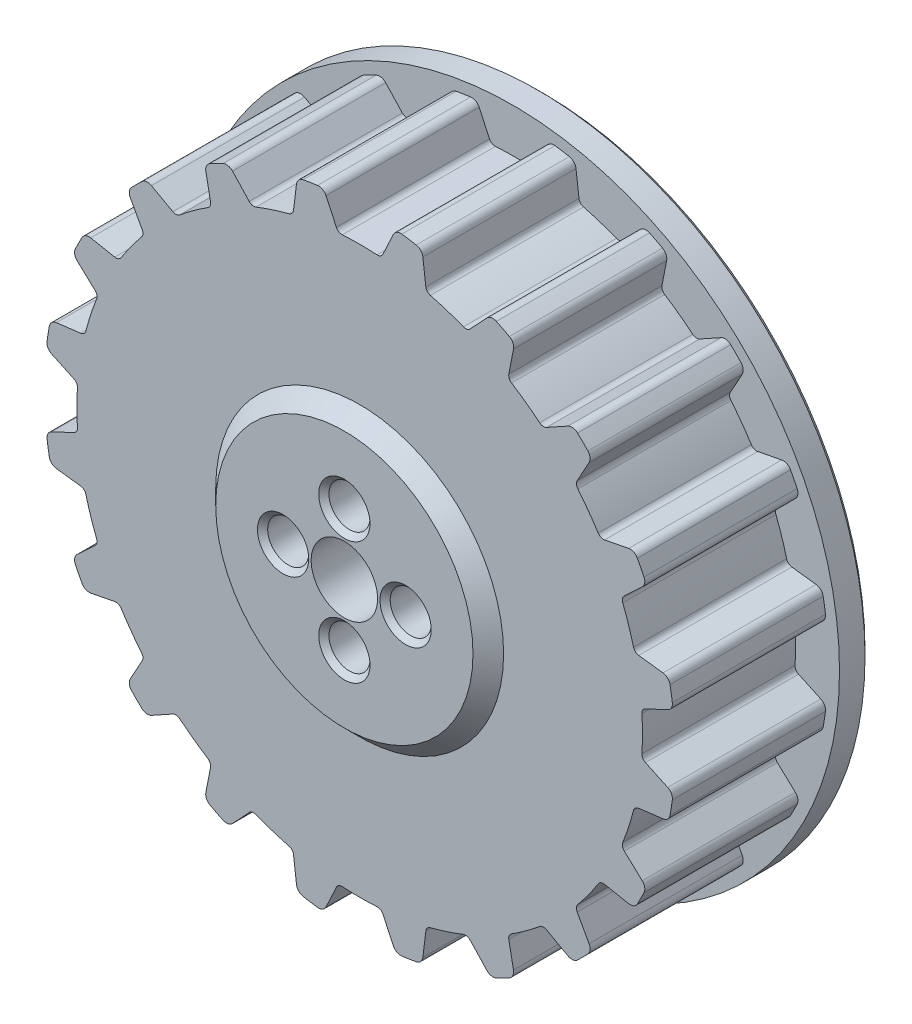
SolidWorks part; units mm, degrees
material "ABS"
ref_plane "正面" through (0, 0, 0) normal (0, 0, 1) x (1, 0, 0)
ref_plane "平面" through (0, 0, 0) normal (0, 1, 0) x (1, 0, 0)
ref_plane "右側面" through (0, 0, 0) normal (1, 0, 0) x (0, 0, -1)
sketch "ｽｹｯﾁ1" plane through (0, 0, 0) normal (0, 0, 1) x (1, 0, 0)
  line L0 (0, 2.608) -> (0, -1.4358) construction
  line L1 (-2.2806, 27.9931) -> (-3.295, 30.1684)
  line L2 (2.2806, 27.9931) -> (3.295, 30.1684)
  line L3 (-4.8338, 30.5196) -> (0, 0) construction
  line L4 (0, 0) -> (4.8338, 30.5196) construction
  line L5 (-4.8338, 30.5196) -> (-0.7822, 4.9384)
  line L6 (0.7822, 4.9384) -> (4.8338, 30.5196)
  arc A0 (1.7, 27.6478) -> (-1.7, 27.6478) centre (0, 0) ccw
  arc A1 (-1.7, 27.6478) -> (-2.2806, 27.9931) centre (-1.7368, 28.2467) cw
  arc A2 (-3.295, 30.1684) -> (-4.1269, 30.6232) centre (-4.02, 29.8303) ccw
  arc A3 (-4.1269, 30.6232) -> (-4.8338, 30.5196) centre (0, 0) ccw
  arc A4 (4.1269, 30.6232) -> (4.8338, 30.5196) centre (0, 0) cw
  arc A5 (3.295, 30.1684) -> (4.1269, 30.6232) centre (4.02, 29.8303) cw
  arc A6 (1.7, 27.6478) -> (2.2806, 27.9931) centre (1.7368, 28.2467) ccw
  arc A7 (-0.7822, 4.9384) -> (0.7822, 4.9384) centre (0, 0) ccw
  dimension "D1" = 3.2
  dimension "D2" = 0.6
  dimension "D3" = 0.8
  dimension "D4" = 30.9
  dimension "D8" = 5
  dimension "D5" = 25
  dimension "D6" = 3.4
  dimension "D7" = 18
extrude "ﾎﾞｽ - 押し出し1" add sketch "ｽｹｯﾁ1" along normal blind 17
pattern_circular "円形ﾊﾟﾀｰﾝ1" count 20 over 360 about axis through (0, 0, 17) along (0, 0, -1) of "ﾎﾞｽ - 押し出し1" reverse direction yes
sketch "ｽｹｯﾁ4" plane through (0, 0, 0) normal (0, 0, -1) x (-1, 0, 0)
  circle A0 centre (0, 0) radius 32
  dimension "D1" = 64
extrude "ﾎﾞｽ - 押し出し3" add sketch "ｽｹｯﾁ4" along normal blind 1
sketch "ｽｹｯﾁ5" plane through (0, 0, 0) normal (0, 0, 1) x (1, 0, 0)
  circle A0 centre (0, 0) radius 32
  circle A1 centre (0, 0) radius 32 construction
extrude "ﾎﾞｽ - 押し出し4" add sketch "ｽｹｯﾁ5" along normal blind 2
sketch "ｽｹｯﾁ2" plane through (0, 0, 17) normal (0, 0, 1) x (1, 0, 0)
  line L0 (0, 0) -> (0, 6) construction
  line L1 (0, 0) -> (6, 0) construction
  line L2 (0, 0) -> (0, -6) construction
  line L3 (0, 0) -> (-6, 0) construction
  circle A0 centre (0, 0) radius 3.25
  circle A1 centre (0, 6) radius 1.6
  circle A2 centre (6, 0) radius 1.6
  circle A3 centre (0, -6) radius 1.6
  circle A4 centre (-6, 0) radius 1.6
  point P17 (0, 0)
  dimension "D1" = 6.5
  dimension "D3" = 3.2
  dimension "D2" = 6
  dimension "D4" = 4
extrude "ｶｯﾄ - 押し出し2" cut sketch "ｽｹｯﾁ2" against normal through all
sketch "ｽｹｯﾁ6" plane through (0, 0, 17) normal (0, 0, 1) x (1, 0, 0)
  circle A0 centre (0, 0) radius 12.5
  circle A1 centre (0, -6) radius 1.6 construction
  circle A2 centre (6, 0) radius 1.6 construction
  circle A3 centre (-6, 0) radius 1.6 construction
  circle A4 centre (0, 0) radius 3.25 construction
  circle A5 centre (0, 6) radius 1.6 construction
  circle A6 centre (0, -6) radius 1.6
  circle A7 centre (6, 0) radius 1.6
  circle A8 centre (-6, 0) radius 1.6
  circle A9 centre (0, 0) radius 3.25
  circle A10 centre (0, 6) radius 1.6
  dimension "D1" = 25
extrude "ﾎﾞｽ - 押し出し5" add sketch "ｽｹｯﾁ6" along normal blind 1.5
sketch "ｽｹｯﾁ9" plane through (0, 0, 18.5) normal (0, 0, 1) x (1, 0, 0)
  circle A0 centre (0, 6) radius 2.01
  circle A1 centre (6, 0) radius 2.01
  circle A2 centre (0, -6) radius 2.01
  circle A3 centre (-6, 0) radius 2.01
  point P12 (0, 0)
  dimension "D1" = 4.02
  dimension "D2" = 4
extrude "ｶｯﾄ - 押し出し4" cut sketch "ｽｹｯﾁ9" against normal blind 5
chamfer "面取り1" distance 0.5 angle 45 4 edges at (-3.99, 0, 18.5) (2.01, -6, 18.5) (8.01, 0, 18.5) (2.01, 6, 18.5)
chamfer "面取り2" distance 1.6 angle 45 1 edges at (12.5, 0, 17)
chamfer "面取り3" distance 0.5 angle 45 6 edges at (-32, 0, -1) (3.25, 0, -1) (-4.4, 0, -1) (1.6, -6, -1) (7.6, 0, -1) (1.6, 6, -1)
